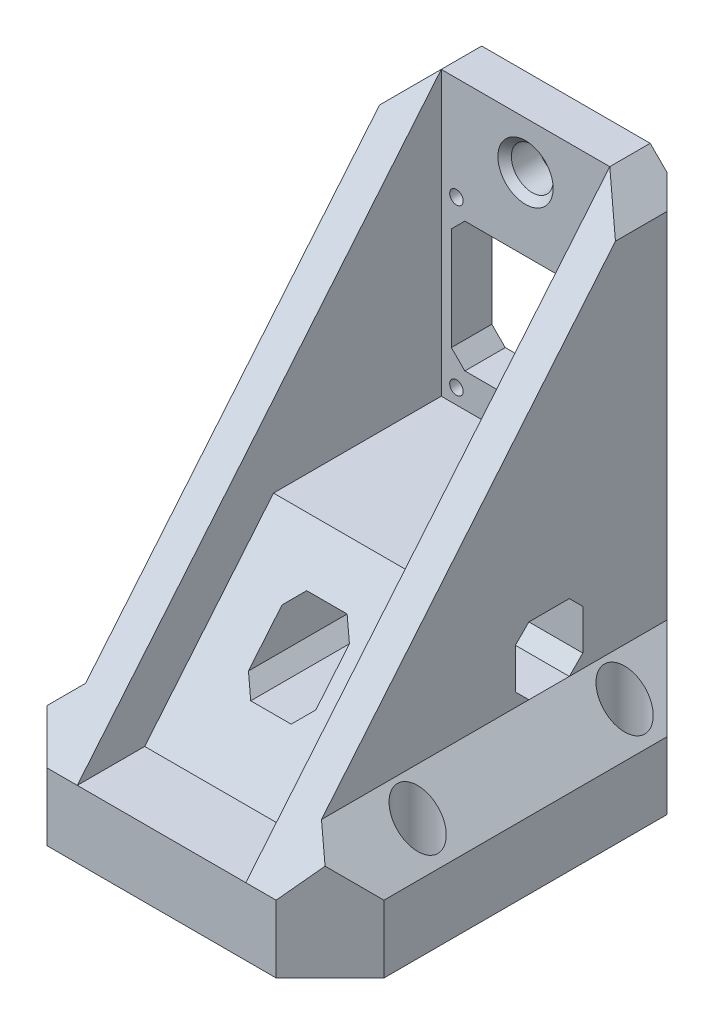
SolidWorks part; units mm, degrees
ref_plane "Front Plane" through (0, 0, 0) normal (0, 0, 1) x (1, 0, 0)
ref_plane "Top Plane" through (0, 0, 0) normal (0, 1, 0) x (1, 0, 0)
ref_plane "Right Plane" through (0, 0, 0) normal (1, 0, 0) x (0, 0, -1)
sketch "Sketch1" plane through (0, 0, 0) normal (0, 1, 0) x (1, 0, 0)
  line L1 (-25, 30) -> (25, 30)
  line L2 (-25, 30) -> (-25, -30)
  line L3 (-25, -30) -> (25, -30)
  line L4 (25, 30) -> (25, -30)
  line L5 (-25, 30) -> (25, -30) construction
  line L6 (-25, -30) -> (25, 30) construction
  point P0 (0, 0)
  dimension "D1" = 50
  dimension "D2" = 60
extrude "Boss-Extrude1" add sketch "Sketch1" along normal blind 10
sketch "Sketch2" plane through (0, 0, 0) normal (0, 1, 0) x (1, 0, 0)
  line L0 (-25, -30) -> (25, -30) construction
  line L1 (-21, -13) -> (21, -13) construction
  line L2 (-21, -13) -> (-21, 17.7) construction
  line L3 (-21, 17.7) -> (21, 17.7) construction
  line L4 (21, -13) -> (21, 17.7) construction
  line L5 (-21, -13) -> (21, 17.7) construction
  line L6 (-21, 17.7) -> (21, -13) construction
  circle A0 centre (-21, 17.7) radius 1.5
  circle A1 centre (-21, -13) radius 1.5
  circle A2 centre (21, 17.7) radius 1.5
  circle A3 centre (21, -13) radius 1.5
  point P0 (0, 2.35)
  dimension "D4" = 3
  dimension "D1" = 42
  dimension "D2" = 30.7
  dimension "D3" = 17
extrude "Cut-Extrude1" cut sketch "Sketch2" along normal blind 6
sketch "Sketch3" plane through (0, 6, 0) normal (0, -1, 0) x (1, 0, 0)
  circle A0 centre (-21, 13) radius 3
  circle A1 centre (21, 13) radius 3
  circle A2 centre (21, -17.7) radius 3
  circle A3 centre (-21, -17.7) radius 3
  dimension "D1" = 6
extrude "Cut-Extrude2" cut sketch "Sketch3" against normal up to next
sketch "Sketch5" plane through (0, 10, 0) normal (0, 1, 0) x (1, 0, 0)
  line L0 (25, 30) -> (-25, 30) construction
  line L1 (-12.5, 24) -> (12.5, 24)
  line L2 (-12.5, 24) -> (-12.5, 30)
  line L3 (-12.5, 30) -> (12.5, 30)
  line L4 (12.5, 24) -> (12.5, 30)
  line L5 (-12.5, 24) -> (12.5, 30) construction
  line L6 (-12.5, 30) -> (12.5, 24) construction
  point P0 (0, 27)
  dimension "D1" = 6
  dimension "D2" = 25
extrude "Boss-Extrude3" add sketch "Sketch5" along normal blind 65
sketch "Sketch6" plane through (0, 0, -30) normal (0, 0, -1) x (-1, 0, 0)
  line L1 (-11, 38) -> (11, 38)
  line L2 (-11, 38) -> (-11, 57.25)
  line L3 (-11, 57.25) -> (11, 57.25)
  line L4 (11, 38) -> (11, 57.25)
  line L5 (-11, 38) -> (11, 57.25) construction
  line L6 (-11, 57.25) -> (11, 38) construction
  line L7 (-12.5, 75) -> (12.5, 75) construction
  point P0 (0, 47.625)
  dimension "D1" = 22
  dimension "D2" = 19.25
  dimension "D3" = 17.75
extrude "Cut-Extrude3" cut sketch "Sketch6" against normal up to next
sketch "Sketch7" plane through (0, 0, -24) normal (0, 0, 1) x (1, 0, 0)
  line L1 (-10.25, 35.25) -> (10.25, 35.25) construction
  line L2 (-10.25, 35.25) -> (-10.25, 59.7) construction
  line L3 (-10.25, 59.7) -> (10.25, 59.7) construction
  line L4 (10.25, 35.25) -> (10.25, 59.7) construction
  line L5 (-10.25, 35.25) -> (10.25, 59.7) construction
  line L6 (-10.25, 59.7) -> (10.25, 35.25) construction
  line L7 (-12.5, 75) -> (12.5, 75) construction
  circle A0 centre (10.25, 35.25) radius 1
  circle A1 centre (-10.25, 35.25) radius 1
  circle A2 centre (-10.25, 59.7) radius 1
  circle A3 centre (10.25, 59.7) radius 1
  point P0 (0, 47.475)
  dimension "D4" = 2
  dimension "D1" = 20.5
  dimension "D2" = 24.45
  dimension "D3" = 15.3
extrude "Cut-Extrude4" cut sketch "Sketch7" against normal blind 2.5
sketch "Sketch8" plane through (0, 0, -26.5) normal (0, 0, 1) x (1, 0, 0)
  circle A0 centre (-10.25, 59.7) radius 2
  circle A1 centre (10.25, 59.7) radius 2
  circle A2 centre (10.25, 35.25) radius 2
  circle A3 centre (-10.25, 35.25) radius 2
  dimension "D1" = 4
extrude "Cut-Extrude5" cut sketch "Sketch8" against normal up to next
sketch "Sketch9" plane through (12.5, 0, 0) normal (1, 0, 0) x (0, 0, -1)
  line L0 (30, 75) -> (24, 75)
  line L4 (-30, 10) -> (30, 10)
  line L5 (30, 10) -> (30, 75)
  line L6 (30, 75) -> (30, 10) construction
  line L8 (-30, 10) -> (24, 75)
extrude "Boss-Extrude4" add sketch "Sketch9" along normal blind 5
mirror "Mirror1" about plane through (0, 0, 0) normal (1, 0, 0) of "Boss-Extrude4"
chamfer "Chamfer1" distance 7.5 angle 45 2 edges at (17.5, 10, 0) (-17.5, 10, 0)
chamfer "Chamfer2" distance 10 angle 45 2 edges at (-25, 5, -30) (25, 5, -30)
chamfer "Chamfer4" distance 5.5 angle 45 1 edges at (0, 0, -30)
chamfer "Chamfer5" distance 5 angle 45 2 edges at (17.5, 75, -25.75) (-17.5, 75, -25.75)
chamfer "Chamfer7" distance 2 angle 45 4 edges at (-11, 57.25, -27) (-11, 38, -27) (11, 38, -27) (11, 57.25, -27)
sketch "Sketch10" plane through (0, 0, -30) normal (0, 0, -1) x (-1, 0, 0)
  circle A0 centre (0, 68) radius 3.1
  circle A1 centre (-10.25, 59.7) radius 2 construction
  dimension "D1" = 6.2
  dimension "D2" = 8.3
extrude "Cut-Extrude6" cut sketch "Sketch10" against normal up to next
chamfer "Chamfer8" distance 1 angle 45 2 edges at (-3.1, 68, -24) (-3.1, 68, -30)
sketch "Sketch11" plane through (-12.5, 0, 0) normal (1, 0, 0) x (0, 0, -1)
  line L0 (-20, 10) -> (24, 10)
  line L1 (24, 10) -> (24, 33)
  line L2 (24, 75) -> (24, 10) construction
  line L3 (24, 33) -> (-0.8923, 33)
  line L4 (30, 38) -> (24, 38) construction
  line L5 (-0.8923, 33) -> (-20, 10)
  line L7 (19.8462, 70) -> (-23.7692, 17.5) construction
  line L9 (-30, 10) -> (20, 10) construction
  dimension "D1" = 5
  dimension "D2" = 10
extrude "Boss-Extrude5" add sketch "Sketch11" along normal up to next
chamfer "Chamfer9" distance 8 angle 45 2 edges at (-25, 5, 30) (25, 5, 30)
sketch "Sketch12" plane through (0, 0, -30) normal (0, 0, -1) x (-1, 0, 0)
  line L1 (-5, 17.5) -> (5, 17.5)
  line L2 (-5, 17.5) -> (-5, 27.5)
  line L3 (-5, 27.5) -> (5, 27.5)
  line L4 (5, 17.5) -> (5, 27.5)
  line L5 (-5, 17.5) -> (5, 27.5) construction
  line L6 (-5, 27.5) -> (5, 17.5) construction
  point P0 (0, 22.5)
  dimension "D1" = 10
extrude "Cut-Extrude7" cut sketch "Sketch12" against normal up to next contours L2 L3 L4 L1
sketch "Sketch14" plane through (-5, 0, 0) normal (1, 0, 0) x (0, 0, -1)
  line L0 (-13.7692, 17.5) -> (30, 17.5) construction
  line L5 (30, 17.5) -> (30, 27.5) construction
  line L6 (-5.4615, 27.5) -> (30, 27.5) construction
  line L7 (5, 17.5) -> (15, 17.5)
  line L8 (5, 17.5) -> (5, 27.5)
  line L9 (5, 27.5) -> (15, 27.5)
  line L10 (15, 17.5) -> (15, 27.5)
  line L11 (5, 17.5) -> (15, 27.5) construction
  line L12 (5, 27.5) -> (15, 17.5) construction
  point P0 (10, 22.5)
  dimension "D1" = 20
extrude "Cut-Extrude9" cut sketch "Sketch14" against normal up to next
mirror "Mirror2" about plane through (0, 0, 0) normal (1, 0, 0) of "Cut-Extrude9"
chamfer "Chamfer11" distance 2 angle 45 20 edges at (11.25, 27.5, -15) (5, 27.5, -22.5) (5, 22.5, -15) (11.25, 17.5, -15) (5, 17.5, -22.5) (-11.25, 17.5, -15) (-5, 17.5, -22.5) (-5, 22.5, -15) (-11.25, 27.5, -15) (-5, 27.5, -22.5) (11.25, 17.5, -5) (5, 17.5, 4.3846) (5, 22.5, -5) (11.25, 27.5, -5) (5, 27.5, 0.2308) (-11.25, 17.5, -5) (-5, 17.5, 4.3846) (-5, 22.5, -5) (-11.25, 27.5, -5) (-5, 27.5, 0.2308)
